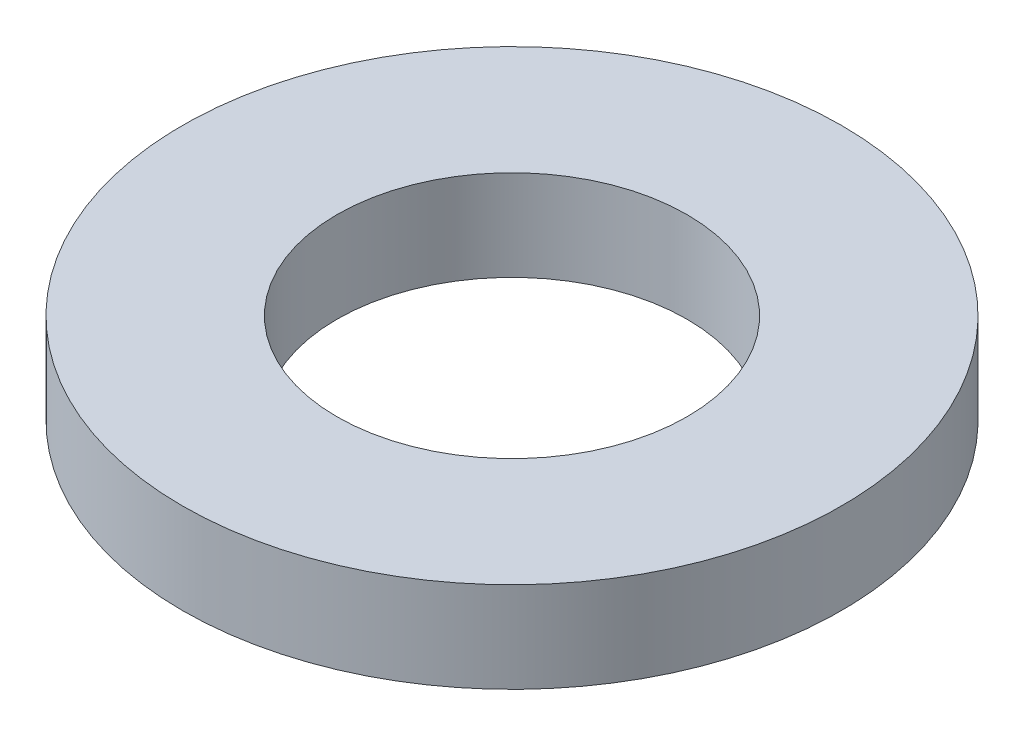
SolidWorks part; units mm, degrees
ref_plane "Front Plane" through (0, 0, 0) normal (0, 0, 1) x (1, 0, 0)
ref_plane "Top Plane" through (0, 0, 0) normal (0, 1, 0) x (1, 0, 0)
ref_plane "Right Plane" through (0, 0, 0) normal (1, 0, 0) x (0, 0, -1)
sketch "Sketch1" plane through (0, 0, 0) normal (0, 1, 0) x (1, 0, 0)
  circle A0 centre (0, 0) radius 80
  dimension "FLANGE_OD" = 160
extrude "Boss-Extrude1" add sketch "Sketch1" along normal blind 22
sketch "Sketch2" plane through (0, 0, 0) normal (0, 1, 0) x (1, 0, 0)
  circle A0 centre (0, 0) radius 42.5
  dimension "BORE_D" = 85
extrude "Cut-Extrude1" cut sketch "Sketch2" along normal through all
sketch "Sketch3" plane through (0, 22, 0) normal (0, 1, 0) x (1, 0, 0)
  circle A0 centre (0, 0) radius 34.9748 construction
  circle A1 centre (-34.9748, 0) radius 3.3846
  dimension "BOLT_D" = 6.7692
  dimension "BOLT_PCD" = 69.9495
extrude "Cut-Extrude2" cut sketch "Sketch3" against normal blind 16.3762 rebuild error yes
pattern_circular "CirPattern1" count 6 over 360 rebuild error yes
